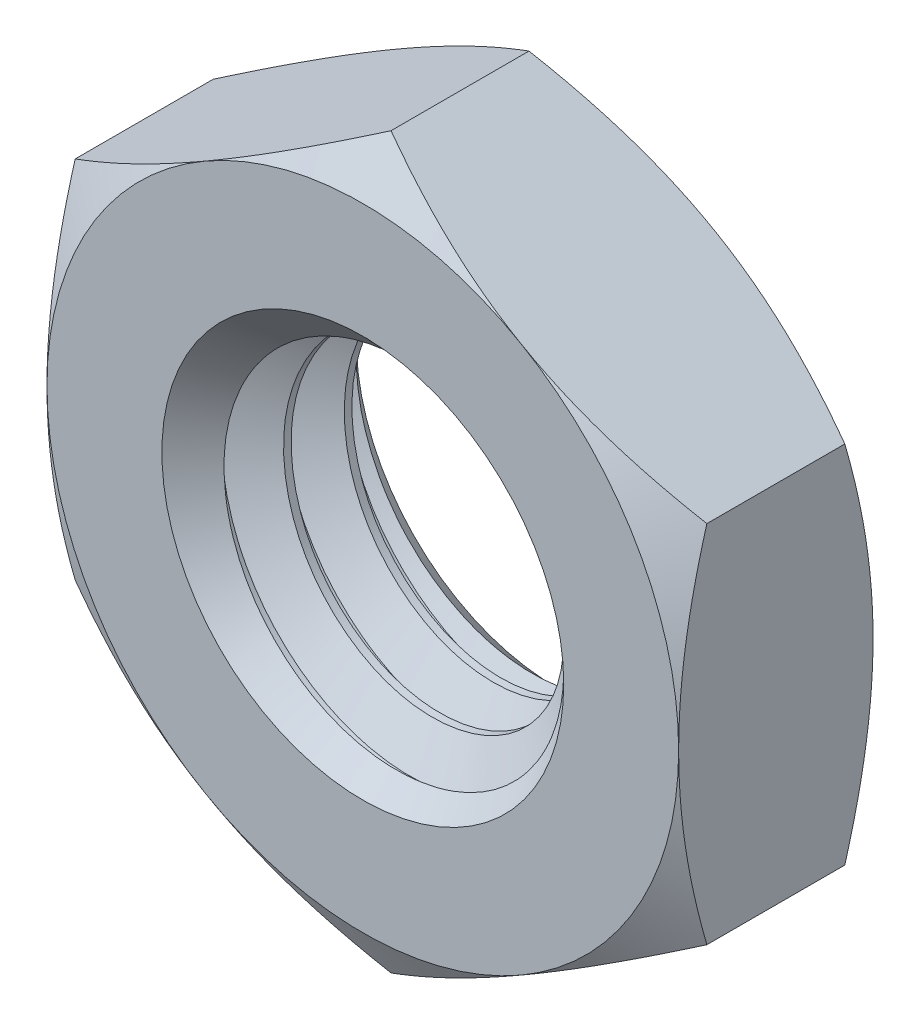
SolidWorks part; units mm, degrees
note: '?' marks a value the reader was unsure of.
ref_plane "Front Plane" through (0, 0, 0) normal (0, 0, 1) x (1, 0, 0)
ref_plane "Top Plane" through (0, 0, 0) normal (0, 1, 0) x (1, 0, 0)
ref_plane "Right Plane" through (0, 0, 0) normal (1, 0, 0) x (0, 0, -1)
sketch "Sketch1" plane through (0, 0, 0) normal (0, 0, 1) x (1, 0, 0)
  line L0 (0, 0) -> (-3.25, -5.6292) construction
  line L1 (0, 7.5056) -> (-6.5, 3.7528) construction
  line L2 (-6.5, 3.7528) -> (-6.5, -3.7528) construction
  line L3 (-6.5, -3.7528) -> (0, -7.5056) construction
  line L4 (0, -7.5056) -> (6.5, -3.7528) construction
  line L5 (6.5, -3.7528) -> (6.5, 3.7528) construction
  line L6 (6.5, 3.7528) -> (0, 7.5056) construction
  circle A0 centre (0, 0) radius 6.5 construction
  circle A1 centre (0, 0) radius 4 construction
  point P10 (-2, -3.4641)
  dimension "Thread Size" = 8
  dimension "Width" = 13
sketch "Sketch2" plane through (0, 0, 0) normal (1, 0, 0) x (0, 0, -1)
  line L0 (-2, 0) -> (2, 0) construction
  line L2 (2, 0) -> (2, 7.5056) construction
  line L3 (2, 7.5056) -> (-2, 7.5056) construction
  line L4 (-2, 7.5056) -> (-2, 0) construction
  line L5 (-2, 0) -> (-2, -7.5056) construction
  line L6 (-2, -7.5056) -> (2, -7.5056) construction
  line L7 (2, -7.5056) -> (2, 0) construction
  line L8 (-2, 4) -> (2, 4) construction
  line L9 (-2, -4) -> (2, -4) construction
  line L11 (-3.1719, 4.1353) -> (-2.5469, 3.0528) construction
  line L12 (-2.5469, 3.0528) -> (-1.9219, 4.1353) construction
  line L13 (-1.9219, 4.1353) -> (-3.1719, 4.1353) construction
  line L14 (-2.5469, 3.0528) -> (-2.5469, 3.1881) construction
  line L15 (-2.625, 3.1881) -> (-2.4688, 3.1881) construction
  line L16 (-2.5469, 4.1353) -> (-2.5469, 4) construction
  line L17 (-3.0938, 4) -> (-2, 4) construction
  line L18 (-2.5469, 4.0677) -> (-1.9609, 4.0677) construction
  line L19 (-2.5469, 4.0677) -> (-3.1328, 4.0677) construction
  point P4 (0, 0)
  point P17 (0, 4)
  point P19 (0, -4)
  dimension "Height" = 4
  dimension "Pitch" = 1.25
  dimension "D1" = 0.1562
sketch "Sketch3" plane through (0, 0, 0) normal (0, 0, 1) x (1, 0, 0)
  line L0 (-6.5, -3.7528) -> (0, -7.5056) construction
  line L1 (0, -7.5056) -> (6.5, -3.7528) construction
  line L2 (6.5, -3.7528) -> (6.5, 3.7528) construction
  line L3 (6.5, 3.7528) -> (0, 7.5056) construction
  line L4 (0, 7.5056) -> (-6.5, 3.7528) construction
  line L5 (-6.5, 3.7528) -> (-6.5, -3.7528) construction
  line L6 (-6.5, -3.7528) -> (0, -7.5056)
  line L7 (0, -7.5056) -> (6.5, -3.7528)
  line L8 (6.5, -3.7528) -> (6.5, 3.7528)
  line L9 (6.5, 3.7528) -> (0, 7.5056)
  line L10 (0, 7.5056) -> (-6.5, 3.7528)
  line L11 (-6.5, 3.7528) -> (-6.5, -3.7528)
  circle A0 centre (0, 0) radius 4 construction
  circle A1 centre (0, 0) radius 4
extrude "Boss-Extrude1" add sketch "Sketch3" against normal up to vertex (2 mm away) from vertex at 2 starting at point (0, 0, 2)
sketch "Sketch4" plane through (0, 0, 0) normal (0, 0, 1) x (1, 0, 0)
  circle A0 centre (0, 0) radius 6.5 construction
  circle A1 centre (0, 0) radius 6.5
extrude "Cut-Extrude1" cut sketch "Sketch4" against normal through all draft 60 from vertex at 2 flip side to cut starting at point (0, 0, 2)
sketch "Sketch5" plane through (0, 0, 0) normal (0, 0, 1) x (1, 0, 0)
  circle A0 centre (0, 0) radius 6.5 construction
  circle A1 centre (0, 0) radius 6.5
extrude "Cut-Extrude2" cut sketch "Sketch5" along normal through all draft 60 from vertex at -2 flip side to cut starting at point (0, 0, -2)
sketch "Sketch6" plane through (0, 0, 2) normal (0, 0, 1) x (1, 0, 0)
  circle A0 centre (0, 0) radius 4
  point P0 (0, 4)
sketch "Sketch8" plane through (0, 0, 0) normal (0, 0, 1) x (1, 0, 0)
  circle A0 centre (0, 0) radius 4.1353
sketch "Sketch9" plane through (0, 0, 0) normal (0, 0, 1) x (1, 0, 0)
  circle A1 centre (0, 0) radius 4.1353
  circle A2 centre (0, 0) radius 4.1353
  dimension "D1" = 0
ref_axis "Center Axis 1" through (0, 0, 2) along (0, 0, -1)?
curve "Helix/Spiral1" pitch 1.25 height 5.25 turns 4.2
sketch "Sketch7" plane through (0, 0, 0) normal (1, 0, 0) x (0, 0, -1)
  line L0 (-3.1328, 4.0677) -> (-2.625, 3.1881)
  line L1 (-2.625, 3.1881) -> (-2.4688, 3.1881)
  line L2 (-2.4688, 3.1881) -> (-1.9609, 4.0677)
  line L3 (-1.9609, 4.0677) -> (-3.1328, 4.0677)
sweep "Sweep1" add profiles "Sketch7" path "Helix/Spiral1"
extrude "Cut-Extrude3" cut sketch "Sketch8" against normal through all draft 45 and the other way through all draft 45 from vertex at 2
extrude "Cut-Extrude4" cut sketch "Sketch9" along normal through all draft 45 and the other way through all draft 45 from vertex at -2
ref_axis "Axis1" through (0, 0, -2.3313) along (0, 0, 1)?
equation "\"D1@Sketch2\"=\"Pitch@Sketch2\"/8"
equation "\"D4@Helix/Spiral1\"=\"Pitch@Sketch2\""
equation "\"D3@Helix/Spiral1\"=\"Height@Sketch2\"+\"Pitch@Sketch2\""
